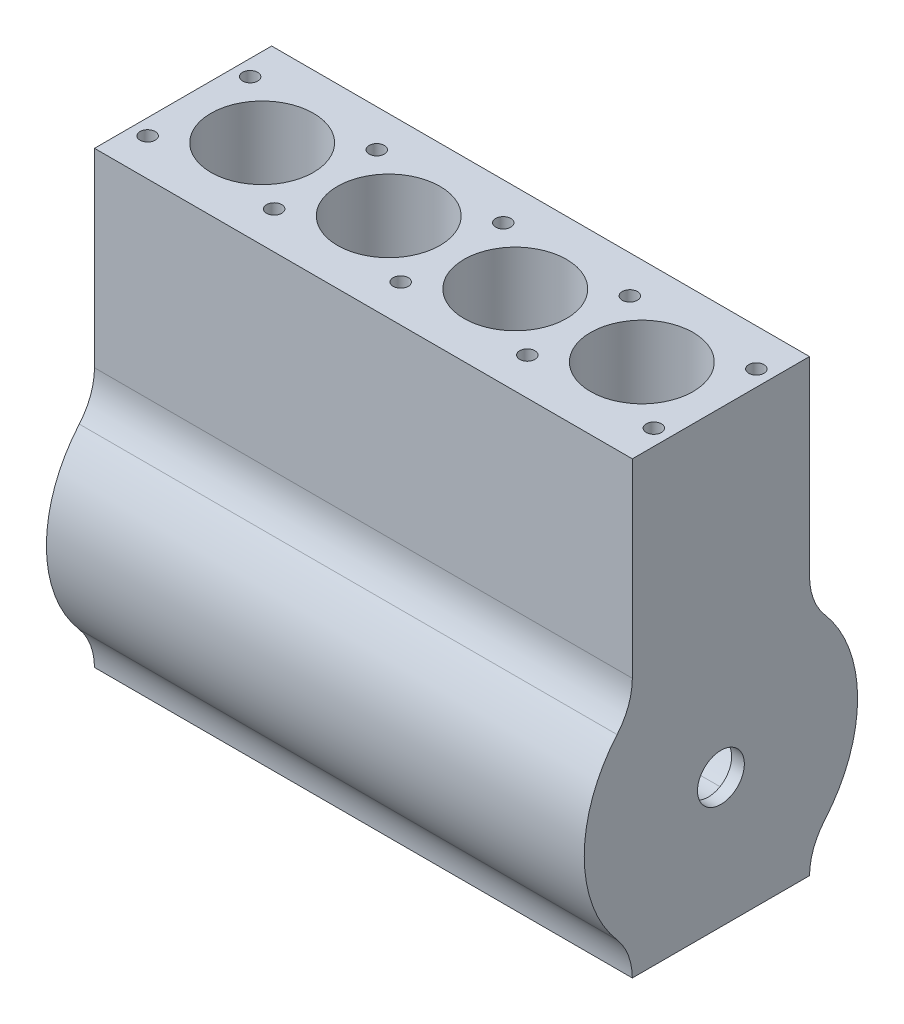
SolidWorks part; units mm, degrees
ref_plane "Front Plane" through (0, 0, 0) normal (0, 0, 1) x (1, 0, 0)
ref_plane "Top Plane" through (0, 0, 0) normal (0, 1, 0) x (1, 0, 0)
ref_plane "Right Plane" through (0, 0, 0) normal (1, 0, 0) x (0, 0, -1)
sketch "Sketch1" plane through (0, 0, 0) normal (0, 1, 0) x (1, 0, 0)
  line L0 (0, 0) -> (62.5, 0)
  line L1 (62.5, 0) -> (162.5, 0)
  line L2 (162.5, 0) -> (262.5, 0)
  line L3 (262.5, 0) -> (362.5, 0)
  line L4 (362.5, 0) -> (425, 0)
  line L5 (0, 0) -> (0, 70) construction
  line L6 (425, 0) -> (425, -70) construction
  line L8 (0, 70) -> (425, 70)
  line L9 (0, 70) -> (0, -70)
  line L10 (0, -70) -> (425, -70)
  line L11 (425, 70) -> (425, -70)
  circle A0 centre (62.5, 0) radius 40.5015
  circle A1 centre (162.5, 0) radius 40.5015
  circle A2 centre (262.5, 0) radius 40.5015
  circle A3 centre (362.5, 0) radius 40.5015
  dimension "D6" = 81.003
  dimension "D7" = 81.003
  dimension "D8" = 81.003
  dimension "D9" = 81.003
  dimension "D1" = 62.5
  dimension "D2" = 100
  dimension "D3" = 100
  dimension "D4" = 100
  dimension "D5" = 62.5
  dimension "D10" = 70
  dimension "D11" = 70
  dimension "D12" = 425
extrude "Boss-Extrude1" add sketch "Sketch1" along normal blind 350 contours A3 L3 A2 L2 A1 L1 A0 L0 L9 L10 L11 L4 | A3 L4 L11 L8 L9 L0 A0 L1 A1 L2 A2 L3 region at (212.5, 0, -44.4413) region at (212.5, 0, 44.4413)
sketch "Sketch2" plane through (0, 0, 0) normal (0, -1, 0) x (1, 0, 0)
  line L14 (415, -60) -> (415, 60)
  line L15 (10, -60) -> (415, -60)
  line L16 (10, 60) -> (10, -60)
  line L17 (415, 60) -> (10, 60)
  line L18 (415, -60) -> (415, 60)
  line L19 (10, -60) -> (415, -60)
  line L20 (10, 60) -> (10, -60)
  line L21 (415, 60) -> (10, 60)
  dimension "D1" = 10
extrude "Cut-Extrude1" cut sketch "Sketch2" against normal blind 250
sketch "Sketch3" plane through (0, 0, 0) normal (-1, 0, 0) x (0, 0, 1)
  circle A0 centre (0, 102.3197) radius 18.5
  dimension "D1" = 37
extrude "Cut-Extrude2" cut sketch "Sketch3" against normal blind 425
sketch "Sketch5" plane through (0, 0, 0) normal (-1, 0, 0) x (0, 0, 1)
  line L0 (-70, 184.5633) -> (-70, 20.0762)
  line L1 (-70, 350) -> (-70, 0) construction
  line L3 (70, 184.5633) -> (70, 20.0762)
  line L5 (70, 350) -> (70, 0) construction
  circle A0 centre (0, 102.3197) radius 108
  dimension "D1" = 216
extrude "Boss-Extrude4" add sketch "Sketch5" against normal blind 425 contours L1 A0 | A0 region at (0, 102.3197, -85.4554) region at (0, 102.3197, 85.4554)
ref_plane "Plane2" through (10, 0, 0) normal (-1, 0, 0) x (0, 0, 1)
sketch "Sketch7" plane through (10, 0, 0) normal (-1, 0, 0) x (0, 0, 1)
  circle A0 centre (0, 102.3197) radius 99
  dimension "D1" = 198
extrude "Cut-Extrude4" cut sketch "Sketch7" against normal blind 405
fillet "Fillet1" radius 20 4 edges at (212.5, 23.5733, -60) (212.5, 23.5733, 60) (212.5, 181.0661, -60) (212.5, 181.0661, 60)
fillet "Fillet2" radius 50 4 edges at (212.5, 20.0762, -70) (212.5, 20.0762, 70) (212.5, 184.5633, 70) (212.5, 184.5633, -70)
sketch "Sketch8" plane through (0, 350, 0) normal (0, 1, 0) x (1, 0, 0)
  line L0 (62.5, 40.5015) -> (362.5, 40.5015) construction
  line L1 (62.5, -40.5015) -> (362.5, -40.5015) construction
  line L2 (62.5, 0) -> (162.5, 0) construction
  line L3 (162.5, 0) -> (262.5, 0) construction
  line L4 (262.5, 0) -> (362.5, 0) construction
  line L5 (112.5, -40.5015) -> (112.5, 40.5015) construction
  line L6 (212.5, -40.5015) -> (212.5, 40.5015) construction
  line L7 (312.5, -40.5015) -> (312.5, 40.5015) construction
  line L8 (62.5, 40.5015) -> (12.5, 40.5015) construction
  line L9 (62.5, -40.5015) -> (12.5, -40.5015) construction
  line L10 (362.5, 40.5015) -> (412.5, 40.5015) construction
  line L11 (362.5, -40.5015) -> (412.5, -40.5015) construction
  line L12 (425, -82.0253) -> (425, -70) construction
  line L13 (0, 70) -> (425, 70)
  line L14 (0, 70) -> (0, -70)
  line L15 (0, -70) -> (425, -70)
  line L16 (425, 70) -> (425, -70)
  line L17 (0, -70) -> (425, -70) construction
  circle A0 centre (62.5, 0) radius 40.5015 construction
  circle A1 centre (362.5, 0) radius 40.5015 construction
  circle A2 centre (112.5, 40.5015) radius 6
  circle A3 centre (112.5, -40.5015) radius 6
  circle A4 centre (212.5, -40.5015) radius 6
  circle A5 centre (212.5, 40.5015) radius 6
  circle A6 centre (312.5, -40.5015) radius 6
  circle A7 centre (312.5, 40.5015) radius 6
  circle A8 centre (12.5, 40.5015) radius 6
  circle A9 centre (12.5, -40.5015) radius 6
  circle A10 centre (412.5, -40.5015) radius 6
  circle A11 centre (412.5, 40.5015) radius 6
  circle A12 centre (62.5, 0) radius 40.5015
  circle A13 centre (162.5, 0) radius 40.5015
  circle A14 centre (262.5, 0) radius 40.5015
  circle A15 centre (362.5, 0) radius 40.5015
  point P17 (112.5, 0)
  point P20 (212.5, 0)
  point P23 (312.5, 0)
  dimension "D4" = 12
  dimension "D5" = 12
  dimension "D6" = 12
  dimension "D7" = 12
  dimension "D8" = 12
  dimension "D9" = 12
  dimension "D14" = 12
  dimension "D15" = 12
  dimension "D16" = 12
  dimension "D17" = 12
  dimension "D1" = 100
  dimension "D2" = 100
  dimension "D3" = 100
  dimension "D10" = 50
  dimension "D11" = 50
  dimension "D12" = 50
  dimension "D13" = 50
extrude "Cut-Extrude5" cut sketch "Sketch8" against normal blind 80 contours A9 | A8 | A2 | A3 | A4 | A5 | A7 | A6 | A10 | A11 region at (112.5, 350, -40.5015) region at (112.5, 350, 40.5015) region at (212.5, 350, 40.5015) region at (212.5, 350, -40.5015) region at (312.5, 350, 40.5015) region at (312.5, 350, -40.5015) region at (12.5, 350, -40.5015) region at (12.5, 350, 40.5015) region at (412.5, 350, 40.5015) region at (412.5, 350, -40.5015)
extrude "Boss-Extrude5" add sketch "Sketch8<3>" along normal blind 5.28
sketch "Sketch8<3>" plane through (0, 350, 0) normal (0, 1, 0) x (1, 0, 0) same geometry as "Sketch8"
